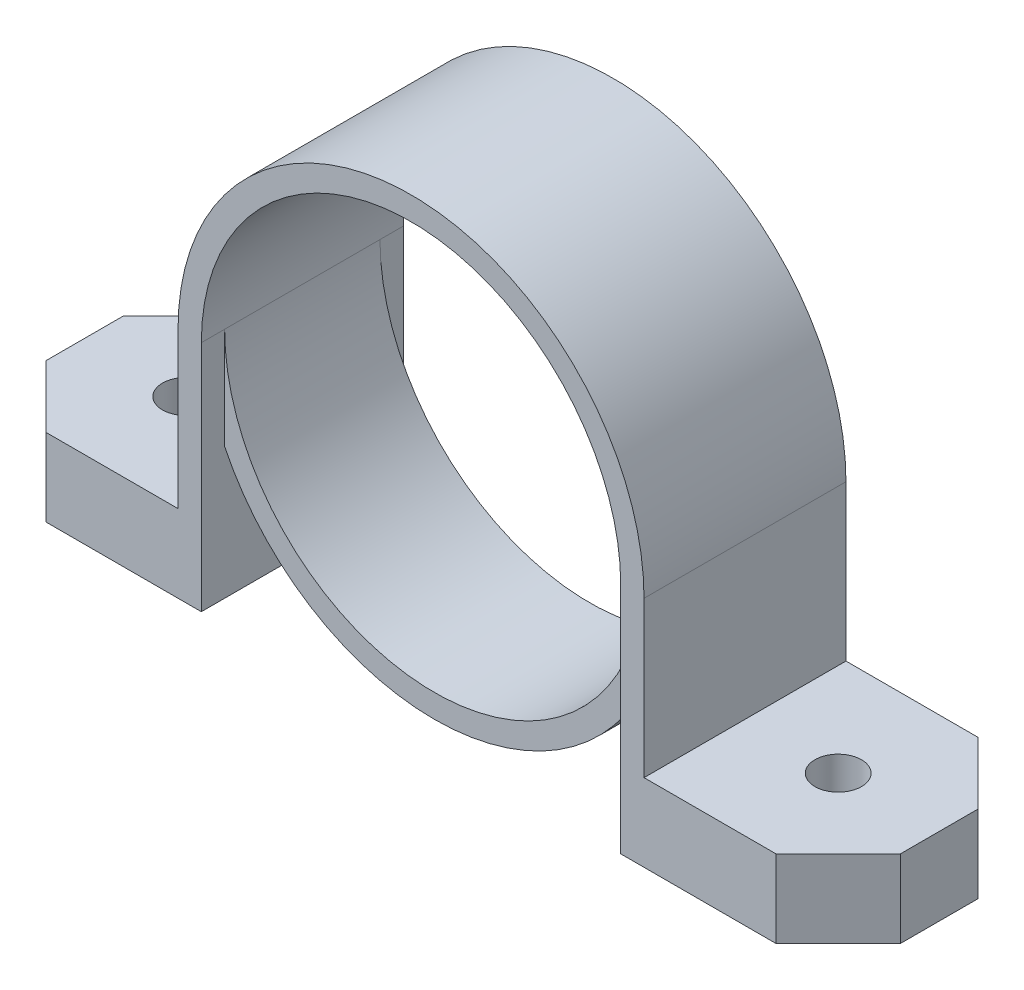
SolidWorks part; units mm, degrees
other "标注1"
sketch "草图3" plane through (-27.5, -15, 6.5) normal (-0.3513, -0.4496, 0.8213) x (-0.5578, -0.604, -0.5693)
ref_plane "前视基准面" through (0, 0, 0) normal (0, 0, 1) x (1, 0, 0)
ref_plane "上视基准面" through (0, 0, 0) normal (0, 1, 0) x (1, 0, 0)
ref_plane "右视基准面" through (0, 0, 0) normal (1, 0, 0) x (0, 0, -1)
sketch "草图1" plane through (0, 0, 0) normal (0, 0, 1) x (1, 0, 0)
  line L0 (-15, 0) -> (-15, -10)
  line L1 (-15, -10) -> (-27.5, -10)
  line L2 (-27.5, -10) -> (-27.5, -15)
  line L3 (-27.5, -15) -> (27.5, -15)
  line L4 (0, 9.4413) -> (0, -23.8066) construction
  line L5 (15, 0) -> (15, -10)
  line L6 (27.5, -10) -> (27.5, -15)
  line L7 (15, -10) -> (27.5, -10)
  line L8 (-13.5, -6.5383) -> (-13.5, -15)
  line L9 (13.5, -6.5383) -> (13.5, -15)
  line L10 (-13.5, -6.5383) -> (-13.5, 0)
  line L11 (13.5, -6.5383) -> (13.5, 0)
  arc A0 (-13.5, -6.5383) -> (13.5, -6.5383) centre (0, 0) ccw
  circle A1 centre (0, 0) radius 4
  circle A2 centre (0, 0) radius 13.5
  arc A3 (15, 0) -> (-15, 0) centre (0, 0) ccw
  point P14 (0, -15)
  dimension "D1" = 30
  dimension "D4" = 8
  dimension "D2" = 5
  dimension "D3" = 55
  dimension "D5" = 1.5
extrude "凸台-拉伸5" add sketch "草图1" along normal blind 6.5 and the other way blind 6.5 contours L4 A3 L0 L1 L2 L3 L8 L10 A2 | A3 L4 A2 L11 L9 L3 L6 L7 L5 region at (0, 14.3735, 0)
extrude "凸台-拉伸6" add sketch "草图1<7>" along normal blind 5 and the other way blind 5 separate body contours L4 A2 L10 A0 | A2 L4 A0 L11 region at (-7.8592, -12.5388, 0) region at (0.2018, -14.25, 0)
sketch "草图1<7>" plane through (0, 0, 0) normal (0, 0, 1) x (1, 0, 0) same geometry as "草图1"
sketch "草图2" plane through (0, -15, 0) normal (0, -1, 0) x (1, 0, 0)
  line L0 (0, 3.507) -> (0, -7.786) construction
  line L1 (-3.6394, 0) -> (-35.5775, 0) construction
  line L2 (-27.5, 2.5) -> (-23.5, 6.5)
  line L3 (-27.5, -6.5) -> (-27.5, 6.5) construction
  line L4 (-27.5, 6.5) -> (-13.5, 6.5) construction
  line L5 (-27.5, 2.5) -> (-27.5, 6.5)
  line L6 (-27.5, 6.5) -> (-23.5, 6.5)
  line L7 (-27.5, -6.5) -> (-23.5, -6.5)
  line L8 (-27.5, -2.5) -> (-27.5, -6.5)
  line L9 (-27.5, -2.5) -> (-23.5, -6.5)
  line L10 (27.5, 6.5) -> (23.5, 6.5)
  line L11 (3.6394, 0) -> (35.5775, 0) construction
  line L12 (27.5, -2.5) -> (23.5, -6.5)
  line L13 (27.5, -2.5) -> (27.5, -6.5)
  line L14 (27.5, -6.5) -> (23.5, -6.5)
  line L15 (27.5, 2.5) -> (27.5, 6.5)
  line L16 (27.5, 2.5) -> (23.5, 6.5)
  circle A0 centre (-21, 0) radius 1.5
  circle A1 centre (21, 0) radius 1.5
  dimension "D1" = 3
  dimension "D2" = 42
  dimension "D3" = 45
  dimension "D4" = 4
extrude "切除-拉伸1" cut sketch "草图2" against normal through all both and the other way through all
